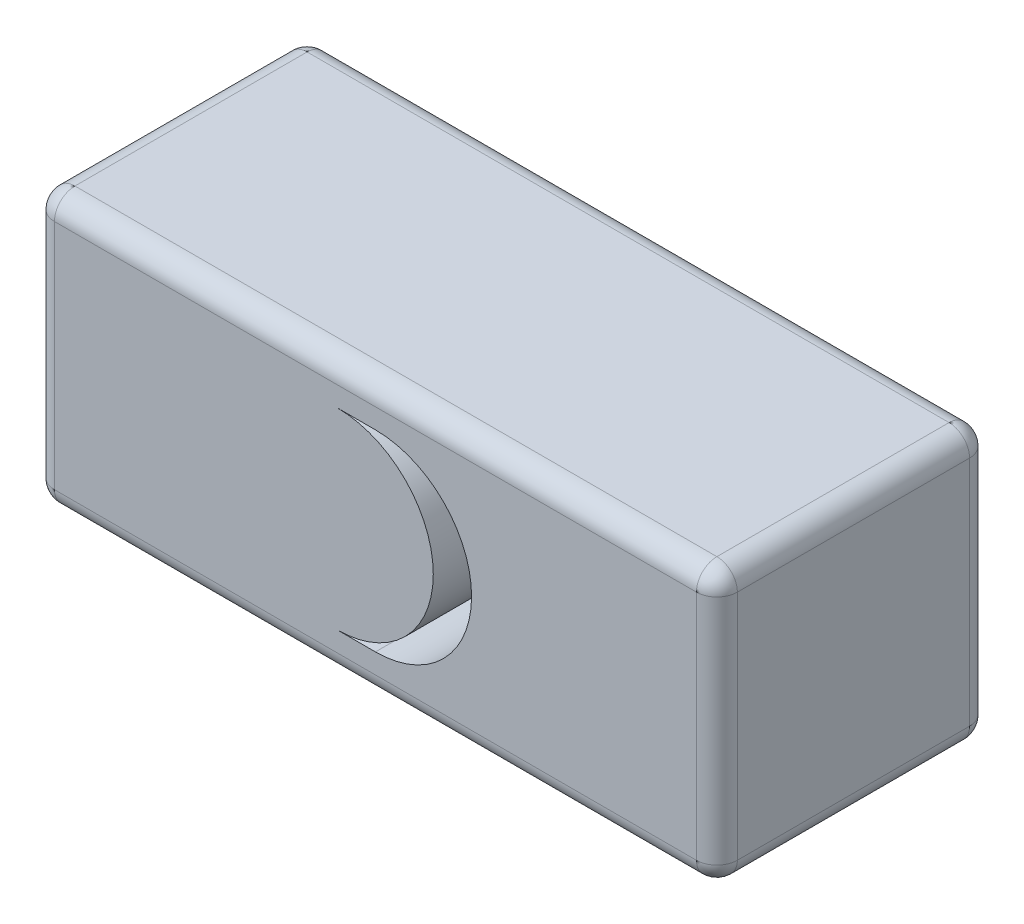
SolidWorks part; units mm, degrees
ref_plane "Plan de face" through (0, 0, 0) normal (0, 0, 1) x (1, 0, 0)
ref_plane "Plan de dessus" through (0, 0, 0) normal (0, 1, 0) x (1, 0, 0)
ref_plane "Plan de droite" through (0, 0, 0) normal (1, 0, 0) x (0, 0, -1)
sketch "Esquisse1" plane through (0, 0, 0) normal (0, 0, 1) x (1, 0, 0)
  line L1 (-0.25, 0.1) -> (0.25, 0.1)
  line L2 (-0.25, 0.1) -> (-0.25, -0.1)
  line L3 (-0.25, -0.1) -> (0.25, -0.1)
  line L4 (0.25, 0.1) -> (0.25, -0.1)
  point P4 (0, 0.1)
  point P6 (-0.25, 0)
  dimension "D1" = 0.5
  dimension "D2" = 0.2
extrude "Boss.-Extru.1" add sketch "Esquisse1" along normal blind 0.1 and the other way blind 0.1
sketch "Esquisse2" plane through (0, 0, 0.1) normal (0, 0, 1) x (1, 0, 0)
  line L0 (0, 0.1) -> (0, -0.1) construction
  line L1 (0.25, 0.1) -> (-0.25, 0.1) construction
  line L2 (-0.25, -0.1) -> (0.25, -0.1) construction
  line L3 (-0.028, 0.0704) -> (0, 0.0704)
  line L4 (-0.028, -0.0704) -> (0, -0.0704)
  arc A0 (0, 0.0704) -> (0, -0.0704) centre (0, 0) cw
  arc A1 (-0.028, 0.0704) -> (-0.028, -0.0704) centre (-0.028, 0) cw
  point P12 (0.0424, 0)
extrude "Enlèv. mat.-Extru.3" cut sketch "Esquisse2" against normal through all
fillet "Congé1" radius 0.015 12 edges at (0, -0.1, 0.1) (0, -0.1, -0.1) (-0.25, 0, 0.1) (-0.25, -0.1, 0) (-0.25, 0, -0.1) (0.25, -0.1, 0) (0.25, 0, 0.1) (0.25, 0, -0.1) (0.25, 0.1, 0) (0, 0.1, 0.1) (-0.25, 0.1, 0) (0, 0.1, -0.1)
